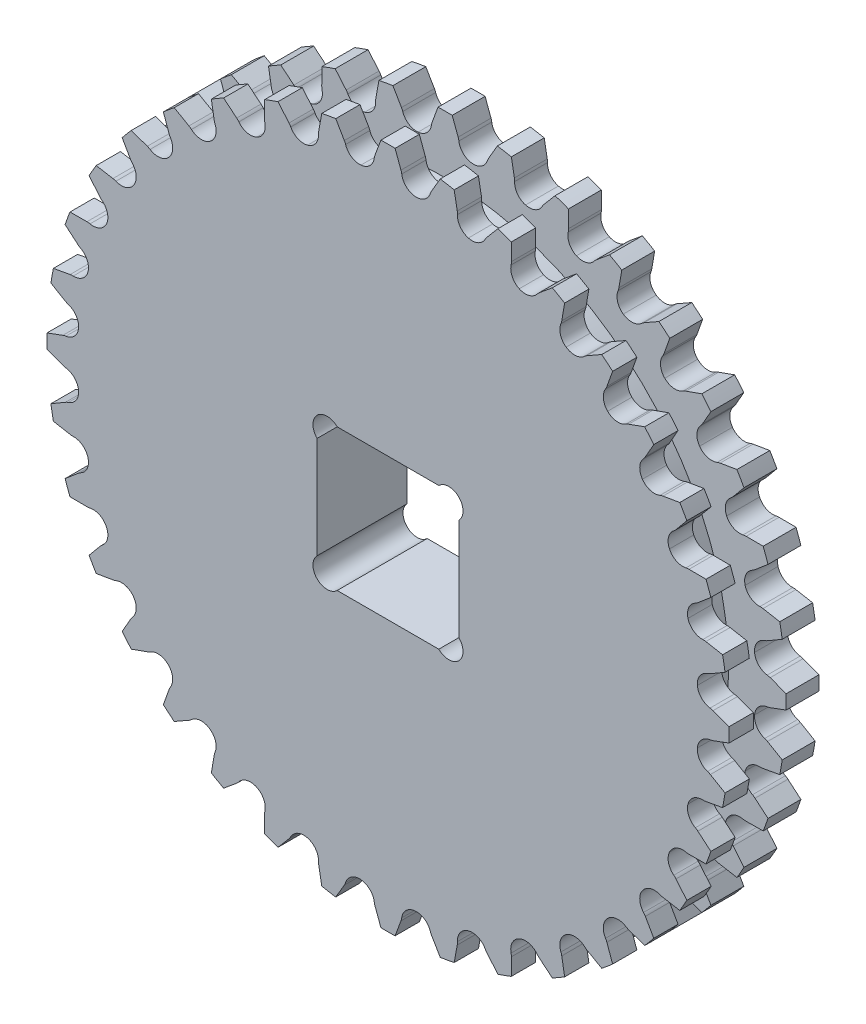
SolidWorks part; units mm, degrees
ref_plane "Front Plane" through (0, 0, 0) normal (0, 0, 1) x (1, 0, 0)
ref_plane "Top Plane" through (0, 0, 0) normal (0, 1, 0) x (1, 0, 0)
ref_plane "Right Plane" through (0, 0, 0) normal (1, 0, 0) x (0, 0, -1)
sketch "Sketch1" plane through (0, 0, 0) normal (0, 0, 1) x (1, 0, 0)
  line L0 (0, 38.2016) -> (0, -38.2016) construction
  line L1 (-3.175, 36.2977) -> (3.175, 36.2977) construction
  line L2 (-0.7937, 38.1934) -> (-1.4554, 36.4072)
  line L3 (-3.175, 36.2977) -> (0, 0) construction
  line L4 (0.7937, 38.1934) -> (1.4554, 36.4072)
  line L5 (3.175, 36.2977) -> (0, 0) construction
  line L6 (-0.7937, 38.1934) -> (0.7937, 38.1934) construction
  line L7 (5.8505, 37.7509) -> (4.8887, 36.1068)
  line L8 (7.4139, 37.4753) -> (7.7554, 35.6014)
  line L9 (12.317, 36.1615) -> (11.0843, 34.7094)
  line L10 (13.8088, 35.6185) -> (13.8197, 33.7138)
  line L11 (18.4093, 33.4733) -> (16.9432, 32.2573)
  line L12 (19.7841, 32.6795) -> (19.4641, 30.8019)
  line L13 (23.9422, 29.768) -> (22.2872, 28.8251)
  line L14 (25.1583, 28.7476) -> (24.517, 26.954)
  line L15 (28.7476, 25.1583) -> (26.954, 24.517)
  line L16 (29.768, 23.9422) -> (28.8251, 22.2872)
  line L17 (32.6795, 19.7841) -> (30.8019, 19.4641)
  line L18 (33.4733, 18.4093) -> (32.2573, 16.9432)
  line L19 (35.6185, 13.8088) -> (33.7138, 13.8197)
  line L20 (36.1615, 12.317) -> (34.7094, 11.0843)
  line L21 (37.4753, 7.4139) -> (35.6014, 7.7554)
  line L22 (37.7509, 5.8505) -> (36.1068, 4.8887)
  line L23 (38.1934, 0.7937) -> (36.4072, 1.4554)
  line L24 (38.1934, -0.7938) -> (36.4072, -1.4554)
  line L25 (37.7509, -5.8505) -> (36.1068, -4.8887)
  line L26 (37.4753, -7.4139) -> (35.6014, -7.7554)
  line L27 (36.1615, -12.317) -> (34.7094, -11.0843)
  line L28 (35.6185, -13.8088) -> (33.7138, -13.8197)
  line L29 (33.4733, -18.4093) -> (32.2573, -16.9432)
  line L30 (32.6795, -19.7841) -> (30.8019, -19.4641)
  line L31 (29.768, -23.9422) -> (28.8251, -22.2872)
  line L32 (28.7476, -25.1583) -> (26.954, -24.517)
  line L33 (25.1583, -28.7476) -> (24.517, -26.954)
  line L34 (23.9422, -29.768) -> (22.2872, -28.8251)
  line L35 (19.7841, -32.6795) -> (19.4641, -30.8019)
  line L36 (18.4093, -33.4733) -> (16.9432, -32.2573)
  line L37 (13.8088, -35.6185) -> (13.8197, -33.7138)
  line L38 (12.317, -36.1615) -> (11.0843, -34.7094)
  line L39 (7.4139, -37.4753) -> (7.7554, -35.6014)
  line L40 (5.8505, -37.7509) -> (4.8887, -36.1068)
  line L41 (0.7937, -38.1934) -> (1.4554, -36.4072)
  line L42 (-0.7938, -38.1934) -> (-1.4554, -36.4072)
  line L43 (-5.8505, -37.7509) -> (-4.8887, -36.1068)
  line L44 (-7.4139, -37.4753) -> (-7.7554, -35.6014)
  line L45 (-12.317, -36.1615) -> (-11.0843, -34.7094)
  line L46 (-13.8088, -35.6185) -> (-13.8197, -33.7138)
  line L47 (-18.4093, -33.4733) -> (-16.9432, -32.2573)
  line L48 (-19.7841, -32.6795) -> (-19.4641, -30.8019)
  line L49 (-23.9422, -29.768) -> (-22.2872, -28.8251)
  line L50 (-25.1583, -28.7476) -> (-24.517, -26.954)
  line L51 (-28.7476, -25.1583) -> (-26.954, -24.517)
  line L52 (-29.768, -23.9422) -> (-28.8251, -22.2872)
  line L53 (-32.6795, -19.7841) -> (-30.8019, -19.4641)
  line L54 (-33.4733, -18.4093) -> (-32.2573, -16.9432)
  line L55 (-35.6185, -13.8088) -> (-33.7138, -13.8197)
  line L56 (-36.1615, -12.317) -> (-34.7094, -11.0843)
  line L57 (-37.4753, -7.4139) -> (-35.6014, -7.7554)
  line L58 (-37.7509, -5.8505) -> (-36.1068, -4.8887)
  line L59 (-38.1934, -0.7937) -> (-36.4072, -1.4554)
  line L60 (-38.1934, 0.7938) -> (-36.4072, 1.4554)
  line L61 (-37.7509, 5.8505) -> (-36.1068, 4.8887)
  line L62 (-37.4753, 7.4139) -> (-35.6014, 7.7554)
  line L63 (-36.1615, 12.317) -> (-34.7094, 11.0843)
  line L64 (-35.6185, 13.8088) -> (-33.7138, 13.8197)
  line L65 (-33.4733, 18.4093) -> (-32.2573, 16.9432)
  line L66 (-32.6795, 19.7841) -> (-30.8019, 19.4641)
  line L67 (-29.768, 23.9422) -> (-28.8251, 22.2872)
  line L68 (-28.7476, 25.1583) -> (-26.954, 24.517)
  line L69 (-25.1583, 28.7476) -> (-24.517, 26.954)
  line L70 (-23.9422, 29.768) -> (-22.2872, 28.8251)
  line L71 (-19.7841, 32.6795) -> (-19.4641, 30.8019)
  line L72 (-18.4093, 33.4733) -> (-16.9432, 32.2573)
  line L73 (-13.8088, 35.6185) -> (-13.8197, 33.7138)
  line L74 (-12.317, 36.1615) -> (-11.0843, 34.7094)
  line L75 (-7.4139, 37.4753) -> (-7.7554, 35.6014)
  line L76 (-5.8505, 37.7509) -> (-4.8887, 36.1068)
  circle A0 centre (0, 0) radius 36.4363 construction
  arc A1 (0.7937, 38.1934) -> (-0.7937, 38.1934) centre (0, 0) ccw
  arc A4 (1.4554, 36.4072) -> (1.5394, 36.0724) centre (-0.0332, 35.8557) cw
  arc A5 (-1.4554, 36.4072) -> (-1.5394, 36.0724) centre (0.0332, 35.8557) ccw
  arc A6 (-3.0311, 34.653) -> (-1.5394, 36.0724) centre (-3.175, 36.2977) ccw
  arc A7 (1.5394, 36.0724) -> (3.0311, 34.653) centre (3.175, 36.2977) ccw construction
  arc A9 (7.4139, 37.4753) -> (5.8505, 37.7509) centre (0, 0) ccw
  arc A10 (7.7554, 35.6014) -> (7.78, 35.257) centre (6.1936, 35.3168) cw
  arc A11 (4.8887, 36.1068) -> (4.7478, 35.7917) centre (6.259, 35.3053) ccw
  arc A13 (13.8088, 35.6185) -> (12.317, 36.1615) centre (0, 0) ccw
  arc A14 (13.8197, 33.7138) -> (13.7841, 33.3704) centre (12.2322, 33.7047) cw
  arc A15 (11.0843, 34.7094) -> (10.8909, 34.4235) centre (12.2946, 33.682) ccw
  arc A16 (9.0037, 33.5999) -> (10.8909, 34.4235) centre (9.431, 35.1946) ccw
  arc A17 (19.7841, 32.6795) -> (18.4093, 33.4733) centre (0, 0) ccw
  arc A18 (19.4641, 30.8019) -> (19.3694, 30.4699) centre (17.8991, 31.0686) cw
  arc A19 (16.9432, 32.2573) -> (16.703, 32.0093) centre (17.9566, 31.0354) ccw
  arc A20 (14.7015, 31.5259) -> (16.703, 32.0093) centre (15.3992, 33.0222) ccw
  arc A21 (25.1583, 28.7476) -> (23.9422, 29.768) centre (0, 0) ccw
  arc A22 (24.517, 26.954) -> (24.3662, 26.6435) centre (23.0222, 27.4884) cw
  arc A23 (22.2872, 28.8251) -> (22.0076, 28.6226) centre (23.0731, 27.4458) ccw
  arc A24 (19.9525, 28.4941) -> (22.0076, 28.6226) centre (20.8995, 29.8465) ccw
  arc A25 (29.768, 23.9422) -> (28.7476, 25.1583) centre (0, 0) ccw
  arc A26 (28.8251, 22.2872) -> (28.6226, 22.0076) centre (27.4458, 23.0731) cw
  arc A27 (26.954, 24.517) -> (26.6435, 24.3662) centre (27.4884, 23.0222) ccw
  arc A28 (24.5974, 24.5965) -> (26.6435, 24.3662) centre (25.7648, 25.7639) ccw
  arc A29 (33.4733, 18.4093) -> (32.6795, 19.7841) centre (0, 0) ccw
  arc A30 (32.2573, 16.9432) -> (32.0093, 16.703) centre (31.0354, 17.9566) cw
  arc A31 (30.8019, 19.4641) -> (30.4699, 19.3694) centre (31.0686, 17.8991) ccw
  arc A32 (28.4948, 19.9515) -> (30.4699, 19.3694) centre (29.8472, 20.8985) ccw
  arc A33 (36.1615, 12.317) -> (35.6185, 13.8088) centre (0, 0) ccw
  arc A34 (34.7094, 11.0843) -> (34.4235, 10.8909) centre (33.682, 12.2946) cw
  arc A35 (33.7138, 13.8197) -> (33.3704, 13.7841) centre (33.7047, 12.2322) ccw
  arc A36 (31.5264, 14.7004) -> (33.3704, 13.7841) centre (33.0228, 15.3981) ccw
  arc A37 (37.7509, 5.8505) -> (37.4753, 7.4139) centre (0, 0) ccw
  arc A38 (36.1068, 4.8887) -> (35.7917, 4.7478) centre (35.3053, 6.259) cw
  arc A39 (35.6014, 7.7554) -> (35.257, 7.78) centre (35.3168, 6.1936) ccw
  arc A40 (33.6002, 9.0025) -> (35.257, 7.78) centre (35.1949, 9.4298) ccw
  arc A41 (38.1934, -0.7938) -> (38.1934, 0.7937) centre (0, 0) ccw
  arc A42 (36.4072, -1.4554) -> (36.0724, -1.5394) centre (35.8557, 0.0332) cw
  arc A43 (36.4072, 1.4554) -> (36.0724, 1.5394) centre (35.8557, -0.0332) ccw
  arc A44 (34.653, 3.0311) -> (36.0724, 1.5394) centre (36.2977, 3.175) ccw
  arc A45 (37.4753, -7.4139) -> (37.7509, -5.8505) centre (0, 0) ccw
  arc A46 (35.6014, -7.7554) -> (35.257, -7.78) centre (35.3168, -6.1936) cw
  arc A47 (36.1068, -4.8887) -> (35.7917, -4.7478) centre (35.3053, -6.259) ccw
  arc A48 (34.6529, -3.0323) -> (35.7917, -4.7478) centre (36.2976, -3.1763) ccw
  arc A49 (35.6185, -13.8088) -> (36.1615, -12.317) centre (0, 0) ccw
  arc A50 (33.7138, -13.8197) -> (33.3704, -13.7841) centre (33.7047, -12.2322) cw
  arc A51 (34.7094, -11.0843) -> (34.4235, -10.8909) centre (33.682, -12.2946) ccw
  arc A52 (33.5999, -9.0037) -> (34.4235, -10.8909) centre (35.1946, -9.431) ccw
  arc A53 (32.6795, -19.7841) -> (33.4733, -18.4093) centre (0, 0) ccw
  arc A54 (30.8019, -19.4641) -> (30.4699, -19.3694) centre (31.0686, -17.8991) cw
  arc A55 (32.2573, -16.9432) -> (32.0093, -16.703) centre (31.0354, -17.9566) ccw
  arc A56 (31.5259, -14.7015) -> (32.0093, -16.703) centre (33.0222, -15.3992) ccw
  arc A57 (28.7476, -25.1583) -> (29.768, -23.9422) centre (0, 0) ccw
  arc A58 (26.954, -24.517) -> (26.6435, -24.3662) centre (27.4884, -23.0222) cw
  arc A59 (28.8251, -22.2872) -> (28.6226, -22.0076) centre (27.4458, -23.0731) ccw
  arc A60 (28.4941, -19.9525) -> (28.6226, -22.0076) centre (29.8465, -20.8995) ccw
  arc A61 (23.9422, -29.768) -> (25.1583, -28.7476) centre (0, 0) ccw
  arc A62 (22.2872, -28.8251) -> (22.0076, -28.6226) centre (23.0731, -27.4458) cw
  arc A63 (24.517, -26.954) -> (24.3662, -26.6435) centre (23.0222, -27.4884) ccw
  arc A64 (24.5965, -24.5974) -> (24.3662, -26.6435) centre (25.7639, -25.7648) ccw
  arc A65 (18.4093, -33.4733) -> (19.7841, -32.6795) centre (0, 0) ccw
  arc A66 (16.9432, -32.2573) -> (16.703, -32.0093) centre (17.9566, -31.0354) cw
  arc A67 (19.4641, -30.8019) -> (19.3694, -30.4699) centre (17.8991, -31.0686) ccw
  arc A68 (19.9515, -28.4948) -> (19.3694, -30.4699) centre (20.8985, -29.8472) ccw
  arc A69 (12.317, -36.1615) -> (13.8088, -35.6185) centre (0, 0) ccw
  arc A70 (11.0843, -34.7094) -> (10.8909, -34.4235) centre (12.2946, -33.682) cw
  arc A71 (13.8197, -33.7138) -> (13.7841, -33.3704) centre (12.2322, -33.7047) ccw
  arc A72 (14.7004, -31.5264) -> (13.7841, -33.3704) centre (15.3981, -33.0228) ccw
  arc A73 (5.8505, -37.7509) -> (7.4139, -37.4753) centre (0, 0) ccw
  arc A74 (4.8887, -36.1068) -> (4.7478, -35.7917) centre (6.259, -35.3053) cw
  arc A75 (7.7554, -35.6014) -> (7.78, -35.257) centre (6.1936, -35.3168) ccw
  arc A76 (9.0025, -33.6002) -> (7.78, -35.257) centre (9.4298, -35.1949) ccw
  arc A77 (-0.7938, -38.1934) -> (0.7937, -38.1934) centre (0, 0) ccw
  arc A78 (-1.4554, -36.4072) -> (-1.5394, -36.0724) centre (0.0332, -35.8557) cw
  arc A79 (1.4554, -36.4072) -> (1.5394, -36.0724) centre (-0.0332, -35.8557) ccw
  arc A80 (3.0311, -34.653) -> (1.5394, -36.0724) centre (3.175, -36.2977) ccw
  arc A81 (-7.4139, -37.4753) -> (-5.8505, -37.7509) centre (0, 0) ccw
  arc A82 (-7.7554, -35.6014) -> (-7.78, -35.257) centre (-6.1936, -35.3168) cw
  arc A83 (-4.8887, -36.1068) -> (-4.7478, -35.7917) centre (-6.259, -35.3053) ccw
  arc A84 (-3.0323, -34.6529) -> (-4.7478, -35.7917) centre (-3.1763, -36.2976) ccw
  arc A85 (-13.8088, -35.6185) -> (-12.317, -36.1615) centre (0, 0) ccw
  arc A86 (-13.8197, -33.7138) -> (-13.7841, -33.3704) centre (-12.2322, -33.7047) cw
  arc A87 (-11.0843, -34.7094) -> (-10.8909, -34.4235) centre (-12.2946, -33.682) ccw
  arc A88 (-9.0037, -33.5999) -> (-10.8909, -34.4235) centre (-9.431, -35.1946) ccw
  arc A89 (-19.7841, -32.6795) -> (-18.4093, -33.4733) centre (0, 0) ccw
  arc A90 (-19.4641, -30.8019) -> (-19.3694, -30.4699) centre (-17.8991, -31.0686) cw
  arc A91 (-16.9432, -32.2573) -> (-16.703, -32.0093) centre (-17.9566, -31.0354) ccw
  arc A92 (-14.7015, -31.5259) -> (-16.703, -32.0093) centre (-15.3992, -33.0222) ccw
  arc A93 (-25.1583, -28.7476) -> (-23.9422, -29.768) centre (0, 0) ccw
  arc A94 (-24.517, -26.954) -> (-24.3662, -26.6435) centre (-23.0222, -27.4884) cw
  arc A95 (-22.2872, -28.8251) -> (-22.0076, -28.6226) centre (-23.0731, -27.4458) ccw
  arc A96 (-19.9525, -28.4941) -> (-22.0076, -28.6226) centre (-20.8995, -29.8465) ccw
  arc A97 (-29.768, -23.9422) -> (-28.7476, -25.1583) centre (0, 0) ccw
  arc A98 (-28.8251, -22.2872) -> (-28.6226, -22.0076) centre (-27.4458, -23.0731) cw
  arc A99 (-26.954, -24.517) -> (-26.6435, -24.3662) centre (-27.4884, -23.0222) ccw
  arc A100 (-24.5974, -24.5965) -> (-26.6435, -24.3662) centre (-25.7648, -25.7639) ccw
  arc A101 (-33.4733, -18.4093) -> (-32.6795, -19.7841) centre (0, 0) ccw
  arc A102 (-32.2573, -16.9432) -> (-32.0093, -16.703) centre (-31.0354, -17.9566) cw
  arc A103 (-30.8019, -19.4641) -> (-30.4699, -19.3694) centre (-31.0686, -17.8991) ccw
  arc A104 (-28.4948, -19.9515) -> (-30.4699, -19.3694) centre (-29.8472, -20.8985) ccw
  arc A105 (-36.1615, -12.317) -> (-35.6185, -13.8088) centre (0, 0) ccw
  arc A106 (-34.7094, -11.0843) -> (-34.4235, -10.8909) centre (-33.682, -12.2946) cw
  arc A107 (-33.7138, -13.8197) -> (-33.3704, -13.7841) centre (-33.7047, -12.2322) ccw
  arc A108 (-31.5264, -14.7004) -> (-33.3704, -13.7841) centre (-33.0228, -15.3981) ccw
  arc A109 (-37.7509, -5.8505) -> (-37.4753, -7.4139) centre (0, 0) ccw
  arc A110 (-36.1068, -4.8887) -> (-35.7917, -4.7478) centre (-35.3053, -6.259) cw
  arc A111 (-35.6014, -7.7554) -> (-35.257, -7.78) centre (-35.3168, -6.1936) ccw
  arc A112 (-33.6002, -9.0025) -> (-35.257, -7.78) centre (-35.1949, -9.4298) ccw
  arc A113 (-38.1934, 0.7938) -> (-38.1934, -0.7937) centre (0, 0) ccw
  arc A114 (-36.4072, 1.4554) -> (-36.0724, 1.5394) centre (-35.8557, -0.0332) cw
  arc A115 (-36.4072, -1.4554) -> (-36.0724, -1.5394) centre (-35.8557, 0.0332) ccw
  arc A116 (-34.653, -3.0311) -> (-36.0724, -1.5394) centre (-36.2977, -3.175) ccw
  arc A117 (-37.4753, 7.4139) -> (-37.7509, 5.8505) centre (0, 0) ccw
  arc A118 (-35.6014, 7.7554) -> (-35.257, 7.78) centre (-35.3168, 6.1936) cw
  arc A119 (-36.1068, 4.8887) -> (-35.7917, 4.7478) centre (-35.3053, 6.259) ccw
  arc A120 (-34.6529, 3.0323) -> (-35.7917, 4.7478) centre (-36.2976, 3.1763) ccw
  arc A121 (-35.6185, 13.8088) -> (-36.1615, 12.317) centre (0, 0) ccw
  arc A122 (-33.7138, 13.8197) -> (-33.3704, 13.7841) centre (-33.7047, 12.2322) cw
  arc A123 (-34.7094, 11.0843) -> (-34.4235, 10.8909) centre (-33.682, 12.2946) ccw
  arc A124 (-33.5999, 9.0037) -> (-34.4235, 10.8909) centre (-35.1946, 9.431) ccw
  arc A125 (-32.6795, 19.7841) -> (-33.4733, 18.4093) centre (0, 0) ccw
  arc A126 (-30.8019, 19.4641) -> (-30.4699, 19.3694) centre (-31.0686, 17.8991) cw
  arc A127 (-32.2573, 16.9432) -> (-32.0093, 16.703) centre (-31.0354, 17.9566) ccw
  arc A128 (-31.5259, 14.7015) -> (-32.0093, 16.703) centre (-33.0222, 15.3992) ccw
  arc A129 (-28.7476, 25.1583) -> (-29.768, 23.9422) centre (0, 0) ccw
  arc A130 (-26.954, 24.517) -> (-26.6435, 24.3662) centre (-27.4884, 23.0222) cw
  arc A131 (-28.8251, 22.2872) -> (-28.6226, 22.0076) centre (-27.4458, 23.0731) ccw
  arc A132 (-28.4941, 19.9525) -> (-28.6226, 22.0076) centre (-29.8465, 20.8995) ccw
  arc A133 (-23.9422, 29.768) -> (-25.1583, 28.7476) centre (0, 0) ccw
  arc A134 (-22.2872, 28.8251) -> (-22.0076, 28.6226) centre (-23.0731, 27.4458) cw
  arc A135 (-24.517, 26.954) -> (-24.3662, 26.6435) centre (-23.0222, 27.4884) ccw
  arc A136 (-24.5965, 24.5974) -> (-24.3662, 26.6435) centre (-25.7639, 25.7648) ccw
  arc A137 (-18.4093, 33.4733) -> (-19.7841, 32.6795) centre (0, 0) ccw
  arc A138 (-16.9432, 32.2573) -> (-16.703, 32.0093) centre (-17.9566, 31.0354) cw
  arc A139 (-19.4641, 30.8019) -> (-19.3694, 30.4699) centre (-17.8991, 31.0686) ccw
  arc A140 (-19.9515, 28.4948) -> (-19.3694, 30.4699) centre (-20.8985, 29.8472) ccw
  arc A141 (-12.317, 36.1615) -> (-13.8088, 35.6185) centre (0, 0) ccw
  arc A142 (-11.0843, 34.7094) -> (-10.8909, 34.4235) centre (-12.2946, 33.682) cw
  arc A143 (-13.8197, 33.7138) -> (-13.7841, 33.3704) centre (-12.2322, 33.7047) ccw
  arc A144 (-14.7004, 31.5264) -> (-13.7841, 33.3704) centre (-15.3981, 33.0228) ccw
  arc A145 (-5.8505, 37.7509) -> (-7.4139, 37.4753) centre (0, 0) ccw
  arc A146 (-4.8887, 36.1068) -> (-4.7478, 35.7917) centre (-6.259, 35.3053) cw
  arc A147 (-7.7554, 35.6014) -> (-7.78, 35.257) centre (-6.1936, 35.3168) ccw
  arc A148 (-9.0025, 33.6002) -> (-7.78, 35.257) centre (-9.4298, 35.1949) ccw
  arc A149 (-3.0311, 34.653) -> (-4.7478, 35.7917) centre (-3.1751, 36.2993) cw
  arc A150 (-10.8909, 34.4235) -> (-9.0025, 33.6002) centre (-9.431, 35.1946) ccw
  arc A151 (-16.703, 32.0093) -> (-14.7004, 31.5264) centre (-15.3992, 33.0222) ccw
  arc A152 (-22.0076, 28.6226) -> (-19.9515, 28.4948) centre (-20.8995, 29.8465) ccw
  arc A153 (-26.6435, 24.3662) -> (-24.5965, 24.5974) centre (-25.7648, 25.7639) ccw
  arc A154 (-30.4699, 19.3694) -> (-28.4941, 19.9525) centre (-29.8472, 20.8985) ccw
  arc A155 (-33.3704, 13.7841) -> (-31.5259, 14.7015) centre (-33.0228, 15.3981) ccw
  arc A156 (-33.5999, 9.0037) -> (-35.257, 7.78) centre (-35.1961, 9.4314) cw
  arc A157 (-34.6529, 3.0323) -> (-36.0724, 1.5394) centre (-36.2992, 3.1764) cw
  arc A158 (-34.653, -3.0311) -> (-35.7917, -4.7478) centre (-36.2993, -3.1751) cw
  arc A159 (-33.6002, -9.0025) -> (-34.4235, -10.8909) centre (-35.1965, -9.4302) cw
  arc A160 (-31.5264, -14.7004) -> (-32.0093, -16.703) centre (-33.0242, -15.3987) cw
  arc A161 (-28.6226, -22.0076) -> (-28.4948, -19.9515) centre (-29.8465, -20.8995) ccw
  arc A162 (-24.5974, -24.5965) -> (-24.3662, -26.6435) centre (-25.7659, -25.765) cw
  arc A163 (-19.9525, -28.4941) -> (-19.3694, -30.4699) centre (-20.9004, -29.8478) cw
  arc A164 (-14.7015, -31.5259) -> (-13.7841, -33.3704) centre (-15.3999, -33.0237) cw
  arc A165 (-9.0037, -33.5999) -> (-7.78, -35.257) centre (-9.4314, -35.1961) cw
  arc A166 (-3.0323, -34.6529) -> (-1.5394, -36.0724) centre (-3.1764, -36.2992) cw
  arc A167 (3.0311, -34.653) -> (4.7478, -35.7917) centre (3.1751, -36.2993) cw
  arc A168 (9.0025, -33.6002) -> (10.8909, -34.4235) centre (9.4302, -35.1965) cw
  arc A169 (16.703, -32.0093) -> (14.7004, -31.5264) centre (15.3992, -33.0222) ccw
  arc A170 (19.9515, -28.4948) -> (22.0076, -28.6226) centre (20.8994, -29.8485) cw
  arc A171 (30.4699, -19.3694) -> (28.4941, -19.9525) centre (29.8472, -20.8985) ccw
  arc A172 (26.6435, -24.3662) -> (24.5965, -24.5974) centre (25.7648, -25.7639) ccw
  arc A173 (33.3704, -13.7841) -> (31.5259, -14.7015) centre (33.0228, -15.3981) ccw
  arc A174 (35.257, -7.78) -> (33.5999, -9.0037) centre (35.1949, -9.4298) ccw
  arc A175 (36.0724, -1.5394) -> (34.6529, -3.0323) centre (36.2977, -3.175) ccw
  arc A176 (35.7917, 4.7478) -> (34.653, 3.0311) centre (36.2976, 3.1763) ccw
  arc A177 (34.4235, 10.8909) -> (33.6002, 9.0025) centre (35.1946, 9.431) ccw
  arc A178 (28.6226, 22.0076) -> (28.4948, 19.9515) centre (29.8465, 20.8995) ccw
  arc A179 (32.0093, 16.703) -> (31.5264, 14.7004) centre (33.0222, 15.3992) ccw
  arc A180 (19.3694, 30.4699) -> (19.9525, 28.4941) centre (20.8985, 29.8472) ccw
  arc A181 (24.5974, 24.5965) -> (24.3662, 26.6435) centre (25.7659, 25.765) cw
  arc A182 (13.7841, 33.3704) -> (14.7015, 31.5259) centre (15.3981, 33.0228) ccw
  arc A183 (9.0037, 33.5999) -> (7.78, 35.257) centre (9.4314, 35.1961) cw
  arc A185 (1.5394, 36.0724) -> (4.7478, 35.7917) centre (3.1756, 36.2978) ccw
  arc A186 (3.0323, 34.6529) -> (4.7478, 35.7917) centre (3.1763, 36.2976) ccw [skipped]
  point P13 (0, 36.2977)
  point P18 (0, 38.1934)
  point P372 (0, 0)
  dimension "D1" = 76.4032
  dimension "D2" = 72.8726
  dimension "D3" = 1.651
  dimension "D5" = 1.5875
  dimension "D7" = 36
  dimension "D4" = 6.35
  dimension "D6" = 1.5875
extrude "Boss-Extrude1" add sketch "Sketch1" along normal blind 2.7178
sketch "Sketch3" plane through (0, 0, 0) normal (0, 0, -1) x (-1, 0, 0)
  circle A0 centre (0, 0) radius 31.75
  dimension "D1" = 63.5
extrude "Boss-Extrude2" add sketch "Sketch3" along normal blind 3.683
extrude "Boss-Extrude3" add sketch "Sketch1<2>" against normal blind 3.683 from surface starting at face at (-31.75, 0, -3.683)
sketch "Sketch1<2>" plane through (0, 0, 0) normal (0, 0, 1) x (1, 0, 0) same geometry as "Sketch1"
sketch "Sketch2" plane through (0, 0, 2.7178) normal (0, 0, 1) x (1, 0, 0)
  line L0 (-6.815, 6.815) -> (-7.9375, 7.9375) construction
  line L1 (-5.6924, 7.9375) -> (5.6924, 7.9375)
  line L2 (-7.9375, 5.6924) -> (-7.9375, -5.6924)
  line L3 (-5.6924, -7.9375) -> (5.6924, -7.9375)
  line L4 (7.9375, 5.6924) -> (7.9375, -5.6924)
  line L5 (-6.815, 6.815) -> (7.9375, -7.9375) construction
  line L6 (-7.9375, -7.9375) -> (6.815, 6.815) construction
  line L7 (-7.9375, 0) -> (7.9375, 0) construction
  line L8 (0, 7.9375) -> (0, -7.9375) construction
  arc A0 (-7.9375, 5.6924) -> (-5.6924, 7.9375) centre (-6.815, 6.815) cw
  arc A1 (7.9375, 5.6924) -> (5.6924, 7.9375) centre (6.815, 6.815) ccw
  arc A2 (7.9375, -5.6924) -> (5.6924, -7.9375) centre (6.815, -6.815) cw
  arc A3 (-7.9375, -5.6924) -> (-5.6924, -7.9375) centre (-6.815, -6.815) ccw
  point P0 (0, 0)
  dimension "D3" = 1.5875
  dimension "D1" = 15.875
  dimension "D2" = 15.875
extrude "Cut-Extrude1" cut sketch "Sketch2" against normal through all
